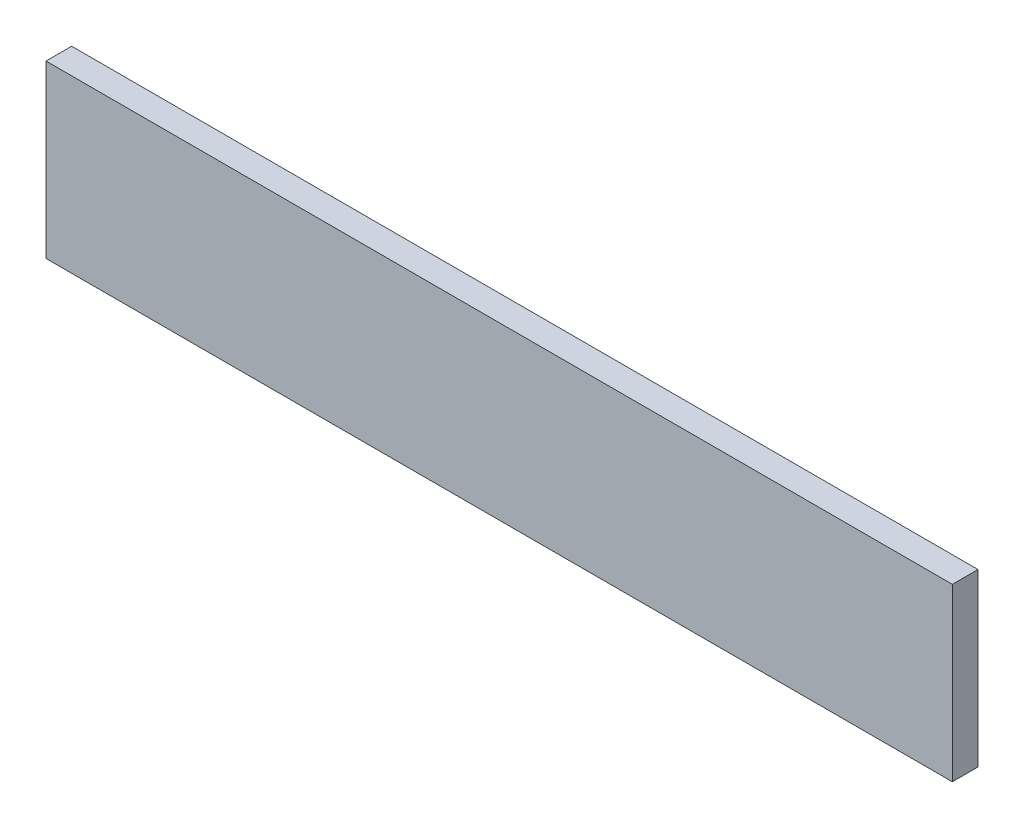
SolidWorks part; units mm, degrees
ref_plane "Ön Düzlem" through (0, 0, 0) normal (0, 0, 1) x (1, 0, 0)
ref_plane "Üst Düzlem" through (0, 0, 0) normal (0, 1, 0) x (1, 0, 0)
ref_plane "Sağ Düzlem" through (0, 0, 0) normal (1, 0, 0) x (0, 0, -1)
sketch "Çizim1" plane through (0, 0, 0) normal (0, 0, 1) x (1, 0, 0)
  line L1 (0, 0) -> (-530, 0)
  line L2 (0, 0) -> (0, -100)
  line L3 (0, -100) -> (-530, -100)
  line L4 (-530, 0) -> (-530, -100)
  dimension "D1" = 530
  dimension "D2" = 100
base flange "Taban-Flanş1" sketch "Çizim1" thickness 15 reverse thickness direction no parameters "D1"=4
sketch "Büküm-Çizgileri1" [suppressed] plane through (0, 0, 0) normal (0, 1, 0) x (1, 0, 0)
sketch "Sınırlandırma-Kutusu1" [suppressed] plane through (0, 0, 0) normal (0, 1, 0) x (1, 0, 0)
sheet metal parameters "Sac-Levha1" thickness 15 parameters "D1"=4
flat pattern "Düz-Çoğaltma1" [suppressed]
sketch "Büküm-Çizgileri2" plane through (0, 0, 0) normal (0, 1, 0) x (1, 0, 0)
sketch3d "Sınırlandırma-Kutusu2" [suppressed]
  line L0 (-530, -100, 0) -> (0, -100, 0) construction
  line L1 (-530, 0, 0) -> (0, 0, 0) construction
  line L2 (-530, -100, 0) -> (-530, 0, 0) construction
  line L3 (0, -100, 0) -> (0, 0, 0) construction
